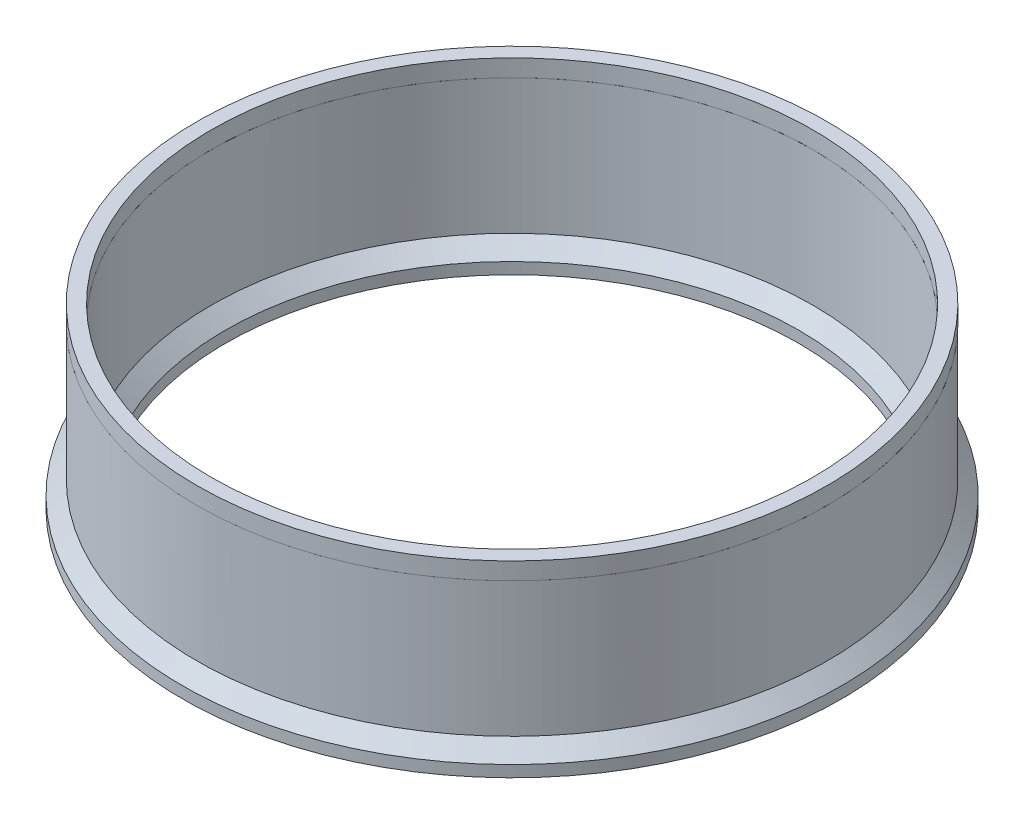
SolidWorks part; units mm, degrees
ref_plane "Front Plane" through (0, 0, 0) normal (0, 0, 1) x (1, 0, 0)
ref_plane "Top Plane" through (0, 0, 0) normal (0, 1, 0) x (1, 0, 0)
ref_plane "Right Plane" through (0, 0, 0) normal (1, 0, 0) x (0, 0, -1)
sketch "Sketch1" plane through (0, 0, 0) normal (0, 1, 0) x (1, 0, 0)
  circle A0 centre (0, 0) radius 55
  circle A1 centre (0, 0) radius 52.5
  dimension "D1" = 110
  dimension "D2" = 105
extrude "Boss-Extrude1" add sketch "Sketch1" along normal mid plane 28
sketch "Sketch2" plane through (0, -14, 0) normal (0, -1, 0) x (1, 0, 0)
  circle A1 centre (0, 0) radius 57.5
  circle A7 centre (0, 0) radius 55
  circle A8 centre (0, 0) radius 55 construction
  circle A9 centre (0, 0) radius 52.5 construction
  circle A10 centre (0, 0) radius 52.5 construction
  circle A12 centre (0, 0) radius 50
  dimension "D1" = 0
  dimension "D2" = 2.5
  dimension "D3" = 2.5
extrude "Boss-Extrude2" add sketch "Sketch2" against normal blind 2
chamfer "Chamfer1" distance 2.5 angle 45 2 edges at (0, -12, -55) (0, -12, -52.5)
sketch "Sketch3" plane through (0, 14, 0) normal (0, 1, 0) x (1, 0, 0)
  circle A0 centre (0, 0) radius 55 construction
  circle A1 centre (0, 0) radius 52.5 construction
  circle A2 centre (0, 0) radius 55
  circle A3 centre (0, 0) radius 52.5
extrude "Boss-Extrude3" add sketch "Sketch3" along normal blind 3 separate body
